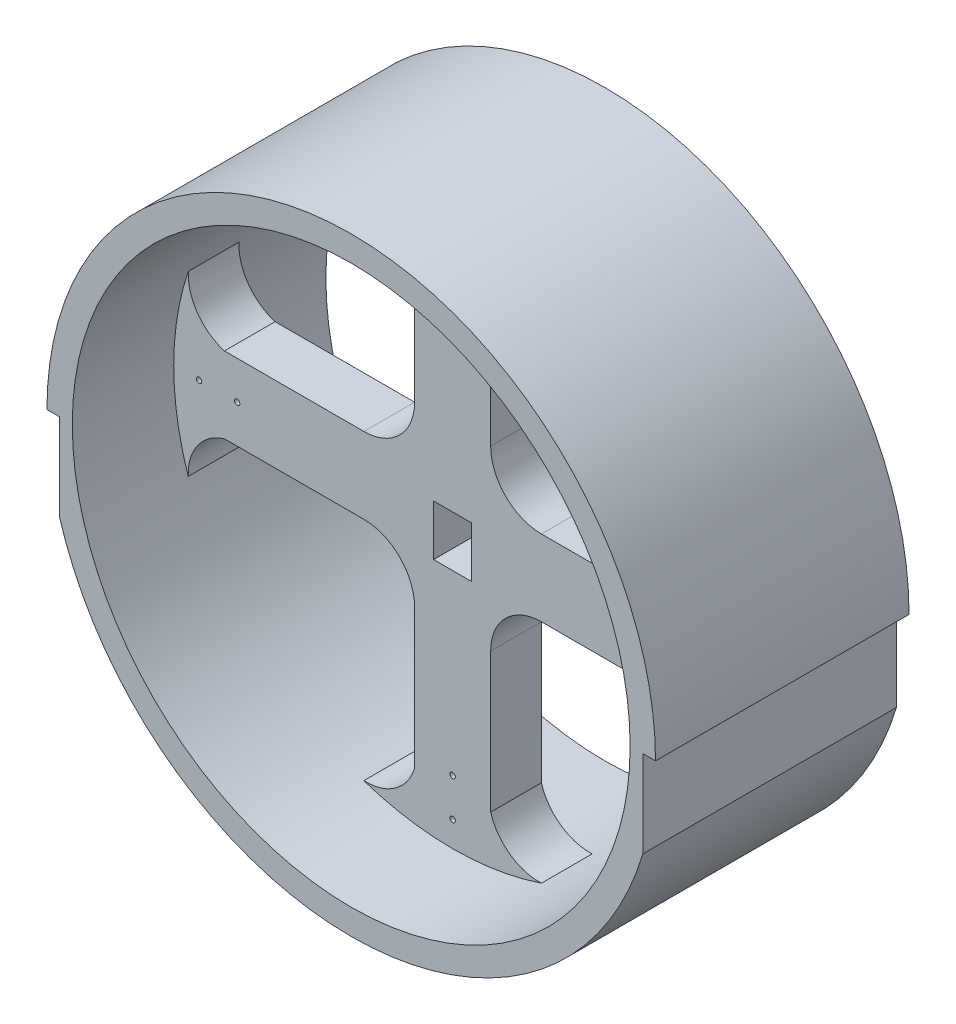
SolidWorks part; units mm, degrees
material "6061 Alloy"
ref_plane "Front Plane" through (0, 0, 0) normal (0, 0, 1) x (1, 0, 0)
ref_plane "Top Plane" through (0, 0, 0) normal (0, 1, 0) x (1, 0, 0)
ref_plane "Right Plane" through (0, 0, 0) normal (1, 0, 0) x (0, 0, -1)
sketch "Sketch1" plane through (0, 0, 0) normal (0, 0, 1) x (1, 0, 0)
  circle A0 centre (0, 0) radius 152.4
  circle A1 centre (0, 0) radius 139.7
  dimension "D1" = 304.8
  dimension "D2" = 279.4
extrude "Boss-Extrude1" add sketch "Sketch1" along normal mid plane 127
sketch "Sketch2" plane through (0, 0, 0) normal (0, 0, 1) x (1, 0, 0)
  line L0 (-114.3, 19.05) -> (-138.7192, 19.05)
  line L1 (-147.1918, -19.05) -> (147.1918, -19.05)
  line L2 (-147.1918, -19.05) -> (-147.1918, 19.05)
  line L3 (-147.1918, 19.05) -> (147.1918, 19.05)
  line L4 (147.1918, -19.05) -> (147.1918, 19.05)
  line L5 (-147.1918, -19.05) -> (147.1918, 19.05) construction
  line L6 (-147.1918, 19.05) -> (147.1918, -19.05) construction
  line L7 (19.05, -143.9568) -> (-19.05, -143.9568)
  line L8 (19.05, -143.9568) -> (19.05, 143.9568)
  line L9 (19.05, 143.9568) -> (-19.05, 143.9568)
  line L10 (-19.05, -143.9568) -> (-19.05, 143.9568)
  line L11 (19.05, -143.9568) -> (-19.05, 143.9568) construction
  line L12 (19.05, 143.9568) -> (-19.05, -143.9568) construction
  line L15 (-44.45, 19.05) -> (-19.05, 19.05)
  line L16 (-19.05, 44.45) -> (-19.05, 19.05)
  line L17 (-132.4254, 44.4927) -> (-143.3503, 19.05)
  line L18 (-143.3503, 19.05) -> (-138.7192, 19.05)
  line L19 (-138.7192, 19.05) -> (-143.3503, 19.05)
  line L20 (-19.05, 114.3) -> (-19.05, 143.9568)
  line L21 (-44.45, 132.4398) -> (-19.05, 143.9568)
  line L22 (44.45, 19.05) -> (19.05, 19.05)
  line L23 (19.05, 44.45) -> (19.05, 19.05)
  line L24 (19.05, 143.3503) -> (19.05, 138.7192)
  line L25 (19.05, 114.3) -> (19.05, 138.7192)
  line L26 (44.4927, 132.4254) -> (19.05, 143.3503)
  line L27 (114.3, 19.05) -> (143.9568, 19.05)
  line L28 (132.4398, 44.45) -> (143.9568, 19.05)
  line L29 (19.05, -44.45) -> (19.05, -19.05)
  line L30 (44.45, -19.05) -> (19.05, -19.05)
  line L31 (143.3503, -19.05) -> (138.7192, -19.05)
  line L32 (114.3, -19.05) -> (138.7192, -19.05)
  line L33 (132.4254, -44.4927) -> (143.3503, -19.05)
  line L34 (19.05, -114.3) -> (19.05, -143.9568)
  line L35 (44.45, -132.4398) -> (19.05, -143.9568)
  line L36 (-44.45, -19.05) -> (-19.05, -19.05)
  line L37 (-19.05, -44.45) -> (-19.05, -19.05)
  line L38 (-19.05, -143.3503) -> (-19.05, -138.7192)
  line L39 (-19.05, -114.3) -> (-19.05, -138.7192)
  line L40 (-44.4927, -132.4254) -> (-19.05, -143.3503)
  line L41 (-114.3, -19.05) -> (-143.9568, -19.05)
  line L42 (-132.4398, -44.45) -> (-143.9568, -19.05)
  arc A1 (-44.45, 19.05) -> (-19.05, 44.45) centre (-44.45, 44.45) ccw
  arc A2 (-114.3, 19.05) -> (-132.4254, 44.4927) centre (-107.0492, 43.3931) cw
  circle A3 centre (0, 0) radius 139.7 construction
  arc A5 (-19.05, 114.3) -> (-44.45, 132.4398) centre (-43.3968, 107.0616) ccw
  arc A6 (19.05, 44.45) -> (44.45, 19.05) centre (44.45, 44.45) ccw
  arc A7 (19.05, 114.3) -> (44.4927, 132.4254) centre (43.3931, 107.0492) cw
  arc A8 (114.3, 19.05) -> (132.4398, 44.45) centre (107.0616, 43.3968) ccw
  arc A9 (44.45, -19.05) -> (19.05, -44.45) centre (44.45, -44.45) ccw
  arc A10 (114.3, -19.05) -> (132.4254, -44.4927) centre (107.0492, -43.3931) cw
  arc A11 (19.05, -114.3) -> (44.45, -132.4398) centre (43.3968, -107.0616) ccw
  arc A12 (-19.05, -44.45) -> (-44.45, -19.05) centre (-44.45, -44.45) ccw
  arc A13 (-19.05, -114.3) -> (-44.4927, -132.4254) centre (-43.3931, -107.0492) cw
  arc A14 (-114.3, -19.05) -> (-132.4398, -44.45) centre (-107.0616, -43.3968) ccw
  point P0 (0, 0)
  point P6 (0, 0)
  point P67 (0, 0)
  dimension "D3" = 25.4
  dimension "D5" = 25.4
  dimension "D1" = 38.1
  dimension "D2" = 38.1
  dimension "D4" = 114.3
  dimension "D6" = 114.3
  dimension "D7" = 4
extrude "Boss-Extrude2" add sketch "Sketch2" along normal mid plane 25.4 contours L1 L10 L3 L2 | L10 L1 L8 L3 | L10 L3 L8 L9 | L8 L1 L4 L3 | L10 L7 L8 L1 | A14 L1 L42 | L10 A13 L40 | A11 L8 L35 | A9 L1 L8 | L1 A10 L33 | A8 L3 L28 | L8 A7 L26 | A5 L10 L21 | L0 A2 L17 L3 | A1 L3 L10 | A6 L8 L3 | A12 L10 L1 region at (-83.1209, 0, 0) region at (-132.2215, 26.1932, 0) region at (-24.7235, 24.7235, 0) region at (0, 81.5034, 0) region at (0, 0, 0) region at (24.7235, 24.7235, 0) region at (83.1209, 0, 0) region at (-24.7235, -24.7235, 0) region at (0, -81.5034, 0) region at (-26.2233, 132.4495, 0) region at (24.7235, -24.7235, 0) region at (-132.4495, -26.2233, 0) region at (132.4495, 26.2233, 0) region at (26.1932, 132.2215, 0) region at (-26.1932, -132.2215, 0) region at (132.2215, -26.1932, 0) region at (26.2233, -132.4495, 0)
sketch "Sketch4" plane through (0, 0, 0) normal (0, 0, 1) x (1, 0, 0)
  line L0 (-9.525, -19.05) -> (-9.525, 0)
  line L5 (-9.525, -19.05) -> (9.525, -19.05)
  line L6 (-9.525, 0) -> (9.525, 0)
  line L7 (9.525, -19.05) -> (9.525, 0)
  line L8 (-9.525, -19.05) -> (9.525, 0) construction
  line L9 (-9.525, 0) -> (9.525, -19.05) construction
  point P1 (0, -9.525)
  dimension "D1" = 19.05
  dimension "D2" = 19.05
  dimension "D3" = 9.525
  dimension "D4" = 0
extrude "Cut-Extrude3" cut sketch "Sketch4" against normal through all both and the other way through all
sketch "Sketch7" plane through (0, 0, 12.7) normal (0, 0, 1) x (1, 0, 0)
  line L0 (-9.525, 0) -> (9.525, 0)
  line L1 (-9.525, 0) -> (-9.525, 6.35)
  line L2 (9.525, 0) -> (9.525, 6.35)
  line L3 (-9.525, 6.35) -> (9.525, 6.35)
  line L4 (9.525, 0) -> (-9.525, 0) construction
  line L5 (-9.525, -19.05) -> (9.525, -19.05) construction
  dimension "D1" = 25.4
extrude "Cut-Extrude4" cut sketch "Sketch7" against normal through all
sketch "Sketch8" plane through (0, 0, 63.5) normal (0, 0, 1) x (1, 0, 0)
  line L0 (-146.05, 0) -> (-163.2527, 0)
  line L1 (-146.05, 0) -> (-146.05, -50.8)
  line L2 (-163.2527, 0) -> (-163.2527, -50.8)
  line L3 (-146.05, -50.8) -> (-163.2527, -50.8)
  circle A0 centre (0, 0) radius 152.4 construction
  dimension "D1" = 50.8
  dimension "D2" = 146.05
extrude "Cut-Extrude5" cut sketch "Sketch8" against normal through all
mirror "Mirror1" about plane through (0, 0, 0) normal (1, 0, 0) of "Cut-Extrude5"
hole_wizard "#4-40 Tapped Hole1" positions "Sketch11" profile "Sketch12" tap size "#4-40" standard "ANSI Inch" end condition through all
sketch "Sketch11" plane through (0, 0, 12.7) normal (0, 0, 1) x (1, 0, 0)
  line L0 (-19.05, 44.45) -> (-19.05, 114.3) construction
  line L1 (44.45, 19.05) -> (114.3, 19.05) construction
  point P0 (-14.2875, 88.9)
  point P2 (-6.0325, 88.9)
  point P4 (88.9, 14.2875)
  point P6 (88.9, 6.0325)
  dimension "D1" = 88.9
  dimension "D2" = 88.9
  dimension "D3" = 8.255
  dimension "D4" = 8.255
  dimension "D5" = 88.9
  dimension "D6" = 4.7625
  dimension "D7" = 4.7625
sketch "Sketch12" plane through (-14.2875, 88.9, 12.7) normal (1, 0, 0) x (0, -1, 0)
  line L0 (0, 0) -> (0, 76.2)
  line L1 (0, 76.2) -> (1.1303, 76.2)
  line L2 (1.1303, 76.2) -> (1.1303, 0)
  line L5 (1.1303, 0) -> (0, 0)
  line L11 (0, -6.35) -> (0, 107.95) construction
  dimension "Thru Tap Drill Dia." = 2.2606
  dimension "Thru Tap Drill Depth" = 76.2
cosmetic thread "Hole Thread1" parameters "D2"=2.8448
cosmetic thread "Hole Thread2" parameters "D2"=2.8448
cosmetic thread "Hole Thread3" parameters "D2"=2.8448
cosmetic thread "Hole Thread4" parameters "D2"=2.8448
hole_wizard "#6-32 Tapped Hole1" positions "Sketch13" profile "Sketch14" tap size "#6-32" standard "ANSI Inch" end condition through all
sketch "Sketch13" plane through (0, 0, 12.7) normal (0, 0, 1) x (1, 0, 0)
  point P0 (-107.95, 0)
  point P2 (-127, 0)
  dimension "D1" = 107.95
  dimension "D2" = 19.05
sketch "Sketch14" plane through (-107.95, 0, 12.7) normal (1, 0, 0) x (0, -1, 0)
  line L0 (0, 0) -> (0, 76.2)
  line L1 (0, 76.2) -> (1.3525, 76.2)
  line L2 (1.3525, 76.2) -> (1.3525, 0)
  line L5 (1.3525, 0) -> (0, 0)
  line L11 (0, -6.35) -> (0, 107.95) construction
  dimension "Thru Tap Drill Dia." = 2.7051
  dimension "Thru Tap Drill Depth" = 76.2
cosmetic thread "Hole Thread5" parameters "D2"=3.5052
cosmetic thread "Hole Thread6" parameters "D2"=3.5052
pattern_circular "CirPattern1" count 4 every 90 about axis through (0, 0, 63.5) along (0, 0, 1) of "#6-32 Tapped Hole1"
